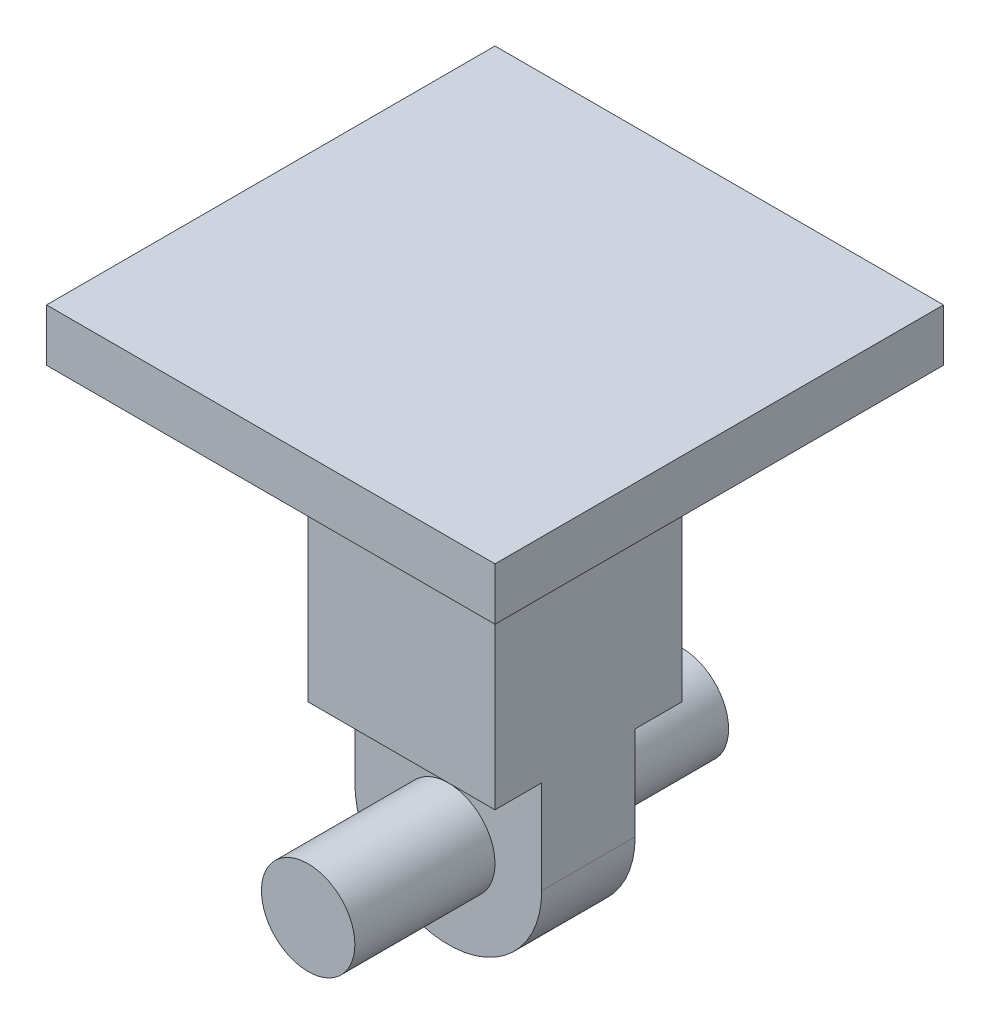
SolidWorks part; units mm, degrees
ref_plane "前视基准面" through (0, 0, 0) normal (0, 0, 1) x (1, 0, 0)
ref_plane "上视基准面" through (0, 0, 0) normal (0, 1, 0) x (1, 0, 0)
ref_plane "右视基准面" through (0, 0, 0) normal (1, 0, 0) x (0, 0, -1)
other "Configuration Table"
sketch "草图1" plane through (0, 0, 0) normal (0, 1, 0) x (1, 0, 0)
  line L1 (-30, -30) -> (30, -30)
  line L2 (-30, -30) -> (-30, 30)
  line L3 (-30, 30) -> (30, 30)
  line L4 (30, -30) -> (30, 30)
  line L5 (-30, -30) -> (30, 30) construction
  line L6 (-30, 30) -> (30, -30) construction
  point P0 (0, 0)
  dimension "D1" = 60
  dimension "D2" = 60
extrude "凸台-拉伸1" add sketch "草图1" along normal blind 7
sketch "草图3" plane through (0, 0, 0) normal (0, 1, 0) x (1, 0, 0)
  line L1 (-12.5, -12.5) -> (12.5, -12.5)
  line L2 (-12.5, -12.5) -> (-12.5, 12.5)
  line L3 (-12.5, 12.5) -> (12.5, 12.5)
  line L4 (12.5, -12.5) -> (12.5, 12.5)
  line L5 (-12.5, -12.5) -> (12.5, 12.5) construction
  line L6 (-12.5, 12.5) -> (12.5, -12.5) construction
  point P0 (0, 0)
  dimension "D1" = 25
  dimension "D2" = 25
extrude "凸台-拉伸2" add sketch "草图3" against normal blind 51.5
sketch "草图4" plane through (0, 0, 0) normal (0, 0, 1) x (1, 0, 0)
  line L0 (-12.5, -51.5) -> (12.5, -51.5) construction
  line L1 (12.5, -51.5) -> (-12.5, -51.5)
  arc A0 (-12.5, -51.5) -> (12.5, -51.5) centre (0, -51.5) ccw
extrude "凸台-拉伸3" add sketch "草图4" against normal up to surface (12.5 mm away) from surface up to face at (0, -25.75, -12.5) starting at face at (0, -25.75, 12.5)
sketch "草图7" plane through (0, 0, 0) normal (0, 1, 0) x (1, 0, 0)
  line L0 (12.5, -12.5) -> (12.5, 12.5) construction
  line L5 (-12.5, 12.5) -> (12.5, 12.5)
  line L6 (-12.5, 12.5) -> (-12.5, 6.25)
  line L7 (-12.5, 6.25) -> (12.5, 6.25)
  line L8 (12.5, 12.5) -> (12.5, 6.25)
  line L10 (-12.5, -12.5) -> (12.5, -12.5)
  line L11 (-12.5, -12.5) -> (-12.5, -6.25)
  line L12 (-12.5, -6.25) -> (12.5, -6.25)
  line L13 (12.5, -12.5) -> (12.5, -6.25)
  dimension "D1" = 6.25
  dimension "D2" = 6.25
extrude "切除-拉伸3" cut sketch "草图7" against normal blind 12.5 and the other way blind 12.5 from vertex starting at point (12.5, -51.5, 12.5)
sketch "草图8" plane through (0, 0, 0) normal (0, 0, 1) x (1, 0, 0)
  arc A0 (-12.5, -51.5) -> (12.5, -51.5) centre (0, -51.5) ccw construction
  arc A1 (-12.5, -51.5) -> (12.5, -51.5) centre (0, -51.5) ccw construction
  circle A2 centre (0, -51.5) radius 6.25
  dimension "D1" = 12.5
extrude "凸台-拉伸4" add sketch "草图8" against normal blind 25 and the other way blind 25
